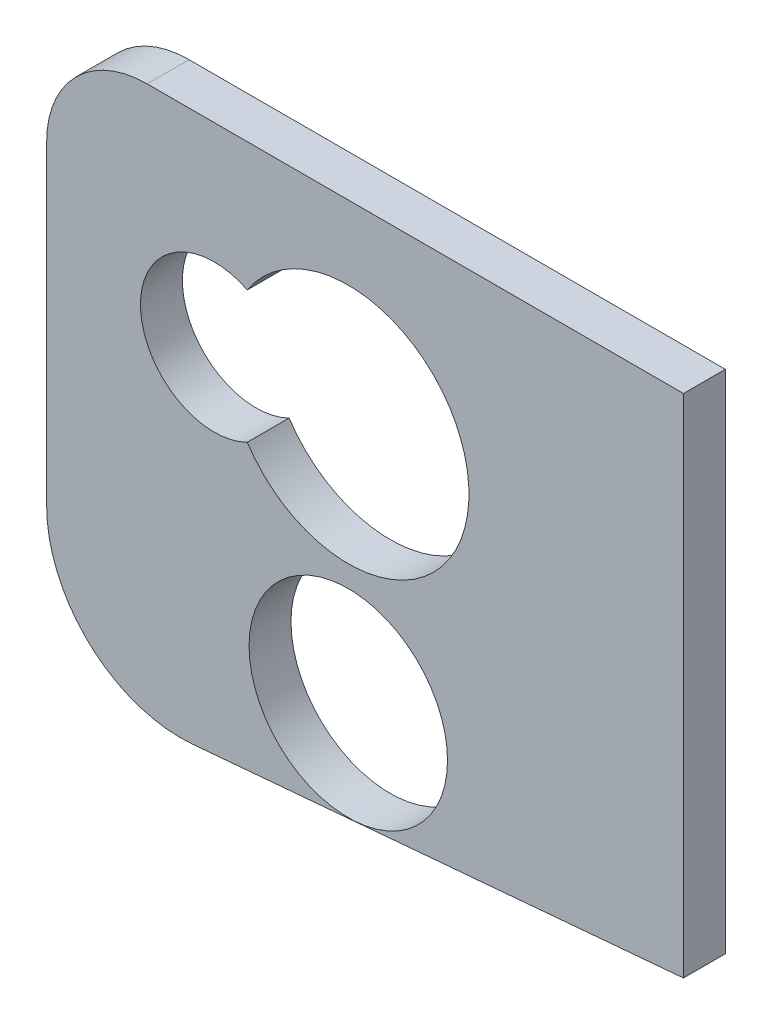
SolidWorks part; units mm, degrees
material "Balsa"
ref_plane "Front Plane" through (0, 0, 0) normal (0, 0, 1) x (1, 0, 0)
ref_plane "Top Plane" through (0, 0, 0) normal (0, 1, 0) x (1, 0, 0)
ref_plane "Right Plane" through (0, 0, 0) normal (1, 0, 0) x (0, 0, -1)
sketch "Sketch1" plane through (0, 0, 0) normal (0, 0, 1) x (1, 0, 0)
  line L0 (0, -1000.1535) -> (0, 48999.8465) construction
  line L2 (-1000, 0) -> (49000, 0) construction
  line L3 (12.7, 16.51) -> (-7.62, 16.51)
  line L4 (12.7, 16.51) -> (12.7, -2.6702)
  line L6 (12.7, -2.6702) -> (-5.9072, -4.2982)
  line L7 (-11.43, 12.7) -> (-11.43, 0.7625)
  circle A0 centre (0, 0) radius 3.7592
  arc A1 (-3.829, 6.6457) -> (-3.829, 11.6423) centre (0, 9.144) ccw
  arc A2 (-3.829, 11.6423) -> (-3.829, 6.6457) centre (-5.08, 9.144) ccw
  arc A3 (-7.62, 16.51) -> (-11.43, 12.7) centre (-7.62, 12.7) ccw
  arc A4 (-5.9072, -4.2982) -> (-11.43, 0.7625) centre (-6.35, 0.7625) cw
  dimension "D1" = 7.5184
  dimension "D4" = 7.366
  dimension "D3" = 9.144
  dimension "D5" = 5.588
  dimension "D9" = 3.81
  dimension "D10" = 5.08
  dimension "D2" = 12.7
  dimension "D6" = 9.144
  dimension "D7" = 5.08
  dimension "D8" = 6.35
  dimension "D11" = 5
  dimension "D12" = 4.2982
extrude "Boss-Extrude1" add sketch "Sketch1" along normal blind 1.5875
